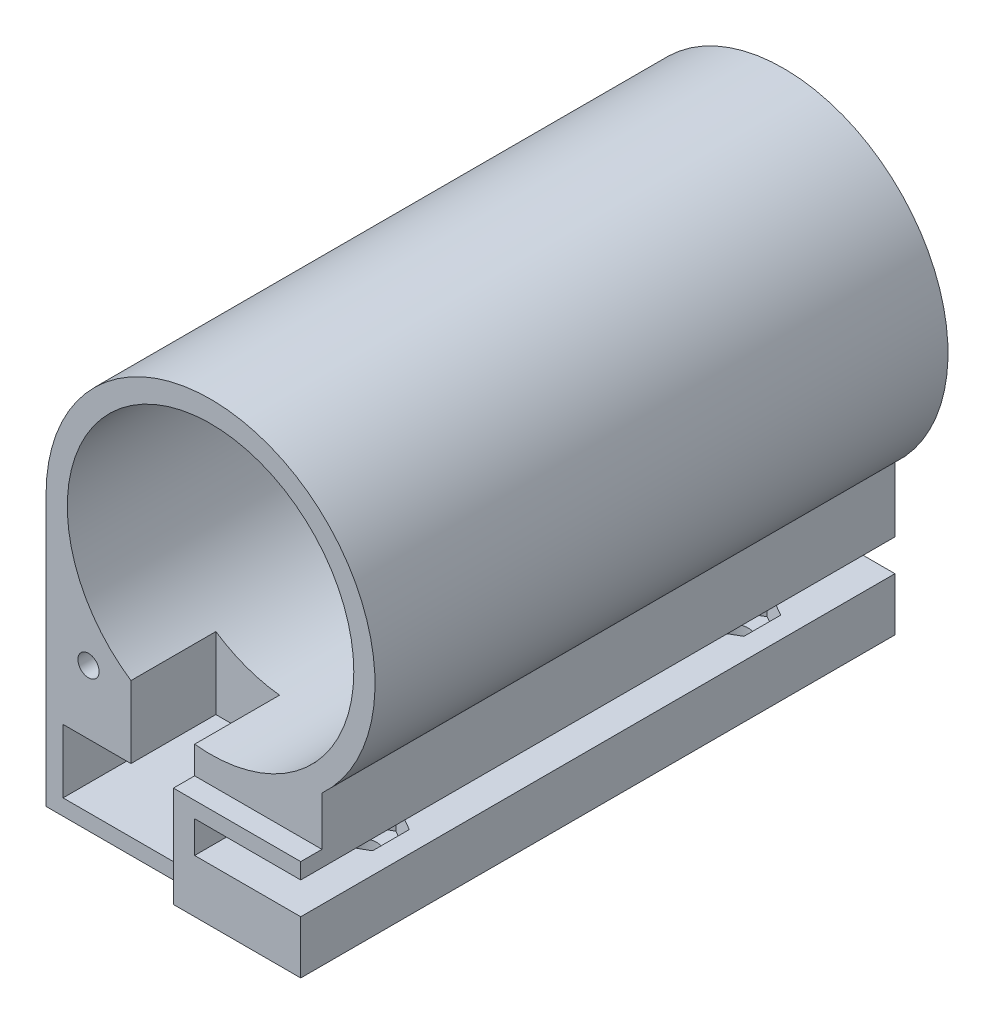
SolidWorks part; units mm, degrees
ref_plane "Plano frontal" through (0, 0, 0) normal (0, 0, 1) x (1, 0, 0)
ref_plane "Plano superior" through (0, 0, 0) normal (0, 1, 0) x (1, 0, 0)
ref_plane "Plano direito" through (0, 0, 0) normal (1, 0, 0) x (0, 0, -1)
sketch "Esboço1" plane through (0, 0, 0) normal (0, 0, 1) x (1, 0, 0)
  line L0 (-0.5, 0) -> (15, 0) construction
  line L2 (-16, 0) -> (-16, -25.5)
  line L3 (-16, -25.5) -> (10, -25.5)
  line L6 (0, -17.5) -> (0, -20.5)
  line L7 (0, -20.5) -> (10, -20.5)
  line L8 (10, -20.5) -> (10, -25.5)
  line L9 (-0.5, 8) -> (-0.5, 11) construction
  line L12 (-2.2, 8) -> (-2.2, 11)
  line L13 (1.2, 8) -> (1.2, 11)
  line L14 (-0.5, -8) -> (-0.5, -11) construction
  line L15 (-2.2, -8) -> (-2.2, -11)
  line L17 (1.2, -8) -> (1.2, -11)
  line L19 (0, -17.5) -> (10, -17.5)
  line L20 (10, -17.5) -> (10, -11.4018)
  line L25 (-14.4, -18) -> (-2, -18)
  line L26 (-14.4, -18) -> (-14.4, -24)
  line L27 (-14.4, -24) -> (-2, -24)
  line L28 (-2, -18) -> (-2, -24)
  line L29 (-14.4, -18) -> (-2, -24) construction
  line L30 (-14.4, -24) -> (-2, -18) construction
  circle A0 centre (-0.5, 0) radius 4.5
  arc A3 (10, -11.4018) -> (-16, 0) centre (-0.5, 0) ccw
  circle A4 centre (-0.5, 0) radius 13.5
  arc A5 (-2.2, 8) -> (1.2, 8) centre (-0.5, 8) ccw
  arc A6 (1.2, 11) -> (-2.2, 11) centre (-0.5, 11) ccw
  arc A7 (-2.2, -8) -> (1.2, -8) centre (-0.5, -8) cw
  arc A8 (1.2, -11) -> (-2.2, -11) centre (-0.5, -11) cw
  arc A9 (-16, 0) -> (10, -11.4018) centre (-0.5, 0) ccw construction
  point P0 (0, 0)
  point P2 (10.1112, -11.4018)
  point P8 (0, 9.4)
  point P11 (-0.5, 9.5)
  point P14 (15, 0)
  point P17 (-17.193, -23.5)
  point P18 (-8.2, -21)
  point P25 (-0.5, -9.5)
  point P30 (-0.5, 15.5)
  point P34 (-16, -7.6994)
  point P35 (-14.7235, -23.5)
  point P41 (-14.8521, -23.5)
  point P42 (-16.1312, -15.5)
  point P43 (0, -19)
  point P44 (-16, -15.5)
  point P45 (-16, -15.5)
  point P46 (-16, -23.7958)
  point P48 (-15.922, -23.5)
  point P49 (0, 0)
  point P50 (-16, 0)
  point P51 (-15.9957, -0.3634)
  dimension "D2" = 9
  dimension "D8" = 1.7
  dimension "D9" = 2
  dimension "D11" = 27
  dimension "D17" = 4
  dimension "D3" = 3
  dimension "D4" = 10
  dimension "D5" = 5
  dimension "D6" = 5
  dimension "D7" = 3
  dimension "D10" = 10
  dimension "D12" = 6
  dimension "D13" = 2
  dimension "D14" = 19
  dimension "D15" = 12.4
  dimension "D16" = 1.5
  dimension "D20" = 19
extrude "Ressalto-extrusão1" add sketch "Esboço1" along normal mid plane 56 contours L3 L8 L7 L6 L2 L25 L28 L27 L26 | L28 L25 L26 L27 | A0 region at (5.5185, 13.7243, 0) region at (-8.2, -21, 0) region at (-13.6182, 0, 0)
extrude "Corte-extrusão5" cut sketch "Esboço1<3>" against normal offset from surface (54 mm away) 2 from surface contours L28 L25 L26 L27 | A0 region at (-8.2, -21, 0) region at (-13.6182, 0, 0) up to face at (2.0906, -14.8132, -28) starting at face at (2.0906, -14.8132, 28)
sketch "Esboço1<3>" plane through (0, 0, 0) normal (0, 0, 1) x (1, 0, 0) same geometry as "Esboço1"
sketch "Esboço3" plane through (0, 0, 28) normal (0, 0, 1) x (1, 0, 0)
  line L5 (-8, -11.225) -> (-8, -18)
  line L13 (-8, -18) -> (-2, -18)
  line L14 (-2, -18) -> (-2, -13.4164)
  line L15 (-2, -13.4164) -> (-8, -11.225)
  line L16 (-14.4, -18) -> (-2, -18) construction
  circle A0 centre (-12, -12) radius 1
  circle A2 centre (-0.5, 0) radius 13.5 construction
  point P2 (-7.3212, -16)
  dimension "D1" = 2
  dimension "D2" = 12
  dimension "D3" = 12
  dimension "D4" = 6
extrude "Corte-extrusão3" cut sketch "Esboço3" against normal blind 10
sketch "Esboço4" plane through (0, 0, 28) normal (0, 0, 1) x (1, 0, 0)
  line L3 (-2, -25.5) -> (-16, -25.5)
  line L4 (-16, -25.5) -> (10, -25.5) construction
  line L7 (-16, -25.5) -> (-16, 0)
  line L8 (10, -11.4018) -> (10, -16)
  line L9 (10, -17.5) -> (10, -11.4018) construction
  line L10 (10, -16) -> (-2, -16)
  line L11 (-2, -24) -> (-2, -13.4164) construction
  line L12 (-2, -16) -> (-2, -25.5)
  line L13 (0, -17.5) -> (10, -17.5) construction
  arc A2 (-16, 0) -> (10, -11.4018) centre (-0.5, 0) cw
  arc A4 (10, -11.4018) -> (-16, 0) centre (-0.5, 0) ccw construction
  dimension "D1" = 1.5
extrude "Corte-extrusão4" cut sketch "Esboço4" against normal blind 2
sketch "Esboço5" plane through (0, -20.5, 0) normal (0, 1, 0) x (1, 0, 0)
  line L0 (0, 0) -> (15.9501, 0) construction
  line L1 (5, 14.0359) -> (8, 15.7679)
  line L2 (8, 15.7679) -> (8, 19.2321)
  line L3 (8, 19.2321) -> (5, 20.9641)
  line L4 (5, 20.9641) -> (2, 19.2321)
  line L5 (2, 19.2321) -> (2, 15.7679)
  line L6 (2, 15.7679) -> (5, 14.0359)
  line L7 (5, -20.9641) -> (8, -19.2321)
  line L8 (8, -19.2321) -> (8, -15.7679)
  line L9 (8, -15.7679) -> (5, -14.0359)
  line L10 (5, -14.0359) -> (2, -15.7679)
  line L11 (2, -15.7679) -> (2, -19.2321)
  line L12 (2, -19.2321) -> (5, -20.9641)
  line L13 (0, -28) -> (10, -28) construction
  circle A0 centre (5, 17.5) radius 3 construction
  circle A1 centre (5, -17.5) radius 3 construction
  circle A2 centre (5, -17.5) radius 1.65
  circle A3 centre (5, 17.5) radius 1.65
  point P21 (5, -28)
  dimension "D1" = 6
  dimension "D3" = 3.3
  dimension "D2" = 35
extrude "Corte-extrusão6" cut sketch "Esboço5" against normal blind 2.5
extrude "Corte-extrusão7" cut sketch "Esboço5<2>" against normal through all contours A2 | A3
sketch "Esboço5<2>" plane through (0, -20.5, 0) normal (0, 1, 0) x (1, 0, 0) same geometry as "Esboço5"
sketch "Esboço6" plane through (0, 0, -26) normal (0, 0, 1) x (1, 0, 0)
  line L1 (-14.4, -24) -> (-9.4, -24)
  line L2 (-14.4, -24) -> (-14.4, -21)
  line L3 (-14.4, -21) -> (-9.4, -21)
  line L4 (-9.4, -24) -> (-9.4, -21)
  dimension "D1" = 5
  dimension "D2" = 3
extrude "Corte-extrusão8" cut sketch "Esboço6" against normal through all
